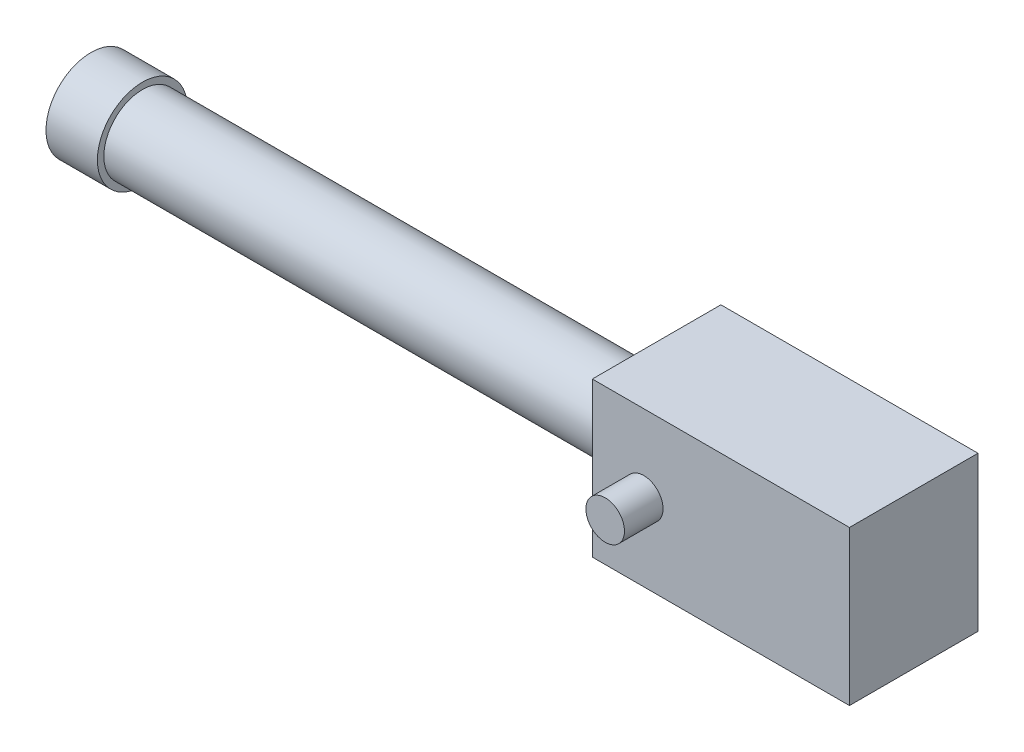
SolidWorks part; units mm, degrees
ref_plane "Front Plane" through (0, 0, 0) normal (0, 0, 1) x (1, 0, 0)
ref_plane "Top Plane" through (0, 0, 0) normal (0, 1, 0) x (1, 0, 0)
ref_plane "Right Plane" through (0, 0, 0) normal (1, 0, 0) x (0, 0, -1)
sketch "Sketch1" plane through (0, 0, 0) normal (0, 0, 1) x (1, 0, 0)
  line L1 (-320.5776, 200.722) -> (679.4224, 200.722)
  line L2 (-320.5776, 200.722) -> (-320.5776, -399.278)
  line L3 (-320.5776, -399.278) -> (679.4224, -399.278)
  line L4 (679.4224, 200.722) -> (679.4224, -399.278)
  dimension "D1" = 1000
  dimension "D2" = 600
extrude "Boss-Extrude1" add sketch "Sketch1" along normal blind 500
sketch "Sketch3" plane through (0, 0, 500) normal (0, 0, 1) x (1, 0, 0)
  line L0 (-320.5776, 200.722) -> (-320.5776, -399.278) construction
  line L1 (679.4224, 200.722) -> (-320.5776, 200.722) construction
  circle A0 centre (-120.5776, -99.278) radius 75
  dimension "D1" = 200
  dimension "D2" = 300
extrude "Boss-Extrude3" add sketch "Sketch3" along normal blind 150
sketch "Sketch4" plane through (0, 0, 0) normal (0, 0, -1) x (-1, 0, 0)
  line L0 (-679.4224, 200.722) -> (320.5776, 200.722) construction
  line L1 (320.5776, 200.722) -> (320.5776, -399.278) construction
  circle A0 centre (120.5776, -99.278) radius 75
  dimension "D1" = 300
  dimension "D2" = 200
extrude "Boss-Extrude4" add sketch "Sketch4" along normal blind 150
sketch "Sketch5" plane through (-320.5776, 0, 0) normal (-1, 0, 0) x (0, 0, 1)
  line L0 (500, 200.722) -> (0, 200.722) construction
  line L1 (0, 200.722) -> (0, -399.278) construction
  circle A0 centre (250, -99.278) radius 150
  dimension "D1" = 300
  dimension "D2" = 250
extrude "Boss-Extrude5" add sketch "Sketch5" along normal blind 2000
sketch "Sketch6" plane through (-2320.5776, 0, 0) normal (-1, 0, 0) x (0, 0, 1)
  circle A0 centre (250, -99.278) radius 175
  circle A1 centre (250, -99.278) radius 150 construction
  dimension "D1" = 0
  dimension "D2" = 350
extrude "Boss-Extrude6" add sketch "Sketch6" along normal blind 200
